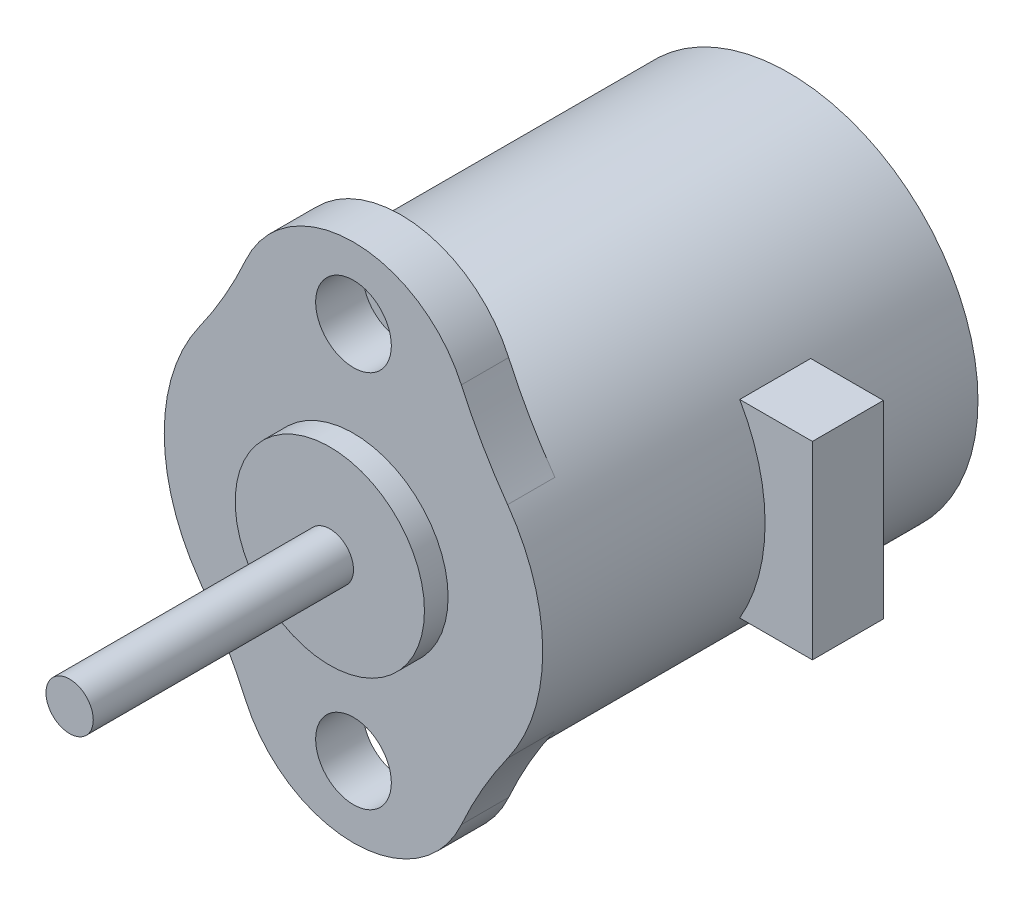
SolidWorks part; units mm, degrees
ref_plane "前视基准面" through (0, 0, 0) normal (0, 0, 1) x (1, 0, 0)
ref_plane "上视基准面" through (0, 0, 0) normal (0, 1, 0) x (1, 0, 0)
ref_plane "右视基准面" through (0, 0, 0) normal (1, 0, 0) x (0, 0, -1)
sketch "草图2" plane through (0, 0, 0) normal (0, 0, 1) x (1, 0, 0)
  circle A0 centre (0, 0) radius 4
  dimension "D1" = 8
extrude "凸台-拉伸1" add sketch "草图2" along normal blind 8.2
sketch "草图4" plane through (0, 0, 8.2) normal (0, 0, 1) x (1, 0, 0)
  circle A0 centre (0, 0) radius 0.5
  dimension "D1" = 1
extrude "凸台-拉伸2" add sketch "草图4" along normal blind 7
sketch "草图5" plane through (0, 0, 8.2) normal (0, 0, 1) x (1, 0, 0)
  circle A0 centre (0, 0) radius 1.5
  dimension "D1" = 3
extrude "凸台-拉伸3" add sketch "草图5" along normal blind 1
sketch "草图6" plane through (0, 0, 0) normal (1, 0, 0) x (0, 0, -1)
  line L0 (-15.7629, 0) -> (1.5629, 0) construction
  line L1 (0, -4) -> (0, 4) construction
  line L2 (-3, -2) -> (-4.5, -2)
  line L3 (-3, -2) -> (-3, 2)
  line L4 (-3, 2) -> (-4.5, 2)
  line L5 (-4.5, -2) -> (-4.5, 2)
  line L6 (-3, -2) -> (-4.5, 2) construction
  line L7 (-3, 2) -> (-4.5, -2) construction
  point P3 (-3.75, 0)
  dimension "D1" = 1.5
  dimension "D2" = 4
  dimension "D3" = 3
extrude "凸台-拉伸4" add sketch "草图6" along normal blind 5
sketch "草图7" plane through (0, 0, 8.2) normal (0, 0, 1) x (1, 0, 0)
  line L0 (-6.7525, 0) -> (6.9406, 0) construction
  circle A0 centre (0, 4) radius 0.8
  arc A1 (2.4969, 3.125) -> (-2.4969, 3.125) centre (0, 3) ccw
  arc A2 (2.4969, -3.125) -> (-2.4969, -3.125) centre (0, -3) cw
  circle A3 centre (0, 0) radius 4
  circle A4 centre (0, 0) radius 4
  circle A5 centre (0, -4) radius 0.8
  circle M3 centre (0, 0) radius 1.5
  circle M4 centre (0, 0) radius 4
  dimension "D1" = 5
  dimension "D3" = 0
  dimension "D4" = 1.6
  dimension "D5" = 1.6
  dimension "D2" = 3
extrude "凸台-拉伸5" add sketch "草图7" along normal blind 1 contours L0 A4 A5 M4 M3 | A5 A2 M4 | L0 A4 A0 M4 M3 | A1 A0 M4 region at (0, 1.7885, 8.2) region at (0, -1.7885, 8.2) region at (1.7172, 3.6738, 8.2) region at (0, -5.4447, 8.2)
cosmetic thread "装饰螺纹线1" parameters "D2"=2.5
cosmetic thread "装饰螺纹线2" parameters "D2"=2.5
fillet "圆角1" radius 10 4 edges at (2.4969, -3.125, 8.7) (2.4969, 3.125, 8.7) (-2.4969, 3.125, 8.7) (-2.4969, -3.125, 8.7)
sketch "草图8" plane through (0, 0, 9.2) normal (0, 0, 1) x (1, 0, 0)
  circle A0 centre (0, 0) radius 2
  dimension "D1" = 4
extrude "凸台-拉伸6" add sketch "草图8" along normal blind 0.5
